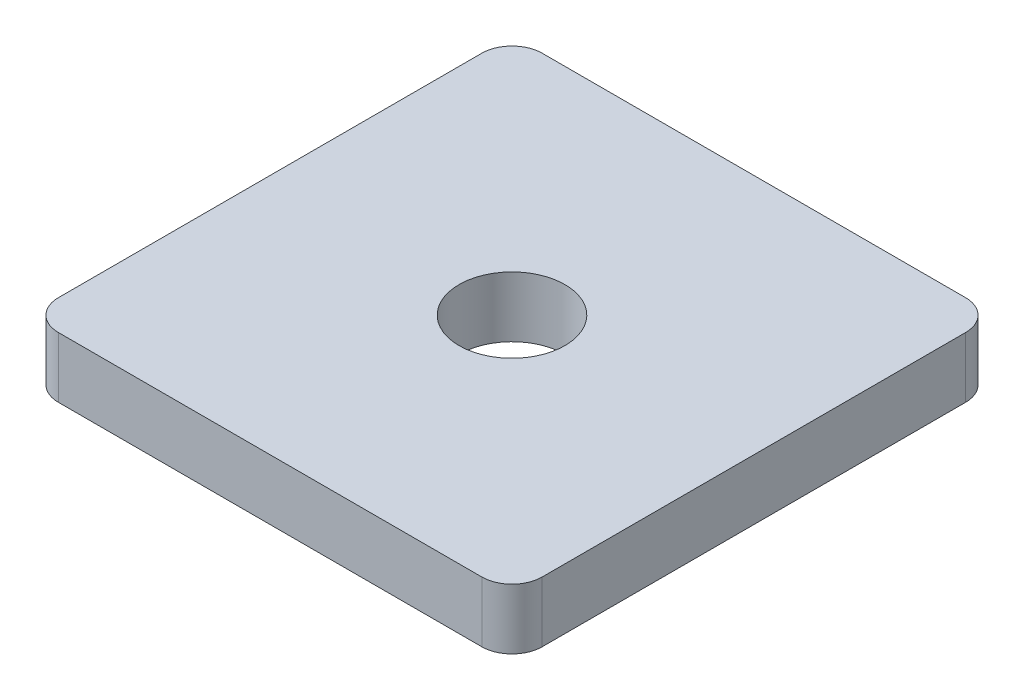
SolidWorks part; units mm, degrees
ref_plane "Front Plane" through (0, 0, 0) normal (0, 0, 1) x (1, 0, 0)
ref_plane "Top Plane" through (0, 0, 0) normal (0, 1, 0) x (1, 0, 0)
ref_plane "Right Plane" through (0, 0, 0) normal (1, 0, 0) x (0, 0, -1)
ref_axis "X-Axis" through (-88.99, 0, 0) along (1, 0, 0)
ref_axis "Y-Axis" through (0, 55, 0) along (0, -1, 0)
ref_axis "Z-Axis" through (0, 0, -88.99) along (0, 0, 1)
sketch "Sketch1" plane through (0, 0, 0) normal (0, 1, 0) x (1, 0, 0)
  line L1 (-8, -8) -> (8, -8)
  line L2 (-8, -8) -> (-8, 8)
  line L3 (-8, 8) -> (8, 8)
  line L4 (8, -8) -> (8, 8)
  line L5 (-8, -8) -> (8, 8) construction
  line L6 (-8, 8) -> (8, -8) construction
  point P0 (0, 0)
  dimension "D1" = 16
extrude "Boss-Extrude1" add sketch "Sketch1" along normal blind 2
fillet "Fillet1" radius 1 4 edges at (-8, 1, -8) (-8, 1, 8) (8, 1, -8) (8, 1, 8)
sketch "Sketch2" plane through (0, 2, 0) normal (0, 1, 0) x (1, 0, 0)
  circle A0 centre (0, 0) radius 1.75
  dimension "D1" = 3.5
extrude "Cut-Extrude1" cut sketch "Sketch2" against normal through all
